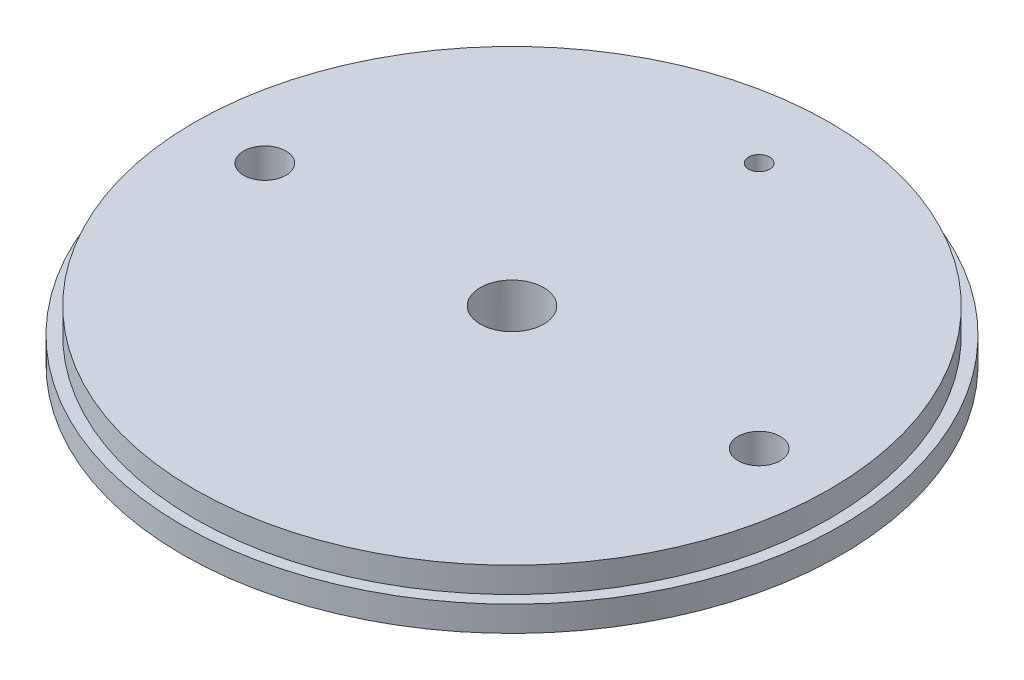
SolidWorks part; units mm, degrees
ref_plane "Front Plane" through (0, 0, 0) normal (0, 0, 1) x (1, 0, 0)
ref_plane "Top Plane" through (0, 0, 0) normal (0, 1, 0) x (1, 0, 0)
ref_plane "Right Plane" through (0, 0, 0) normal (1, 0, 0) x (0, 0, -1)
sketch "Sketch9" plane through (0, 0, 0) normal (0, 1, 0) x (1, 0, 0)
  circle A0 centre (0, 0) radius 49.53
  dimension "D1" = 99.06
extrude "Boss-Extrude1" add sketch "Sketch9" along normal blind 3.81
sketch "Sketch10" plane through (0, 3.81, 0) normal (0, 1, 0) x (1, 0, 0)
  circle A0 centre (0, 0) radius 47.752
  dimension "D1" = 95.504
extrude "Boss-Extrude2" add sketch "Sketch10" along normal blind 3.81
sketch "Sketch11" plane through (0, 0, 0) normal (0, -1, 0) x (-1, 0, 0)
  circle A0 centre (0, 0) radius 37.1475
  circle A1 centre (-37.1475, 0) radius 3.175
  circle A2 centre (37.1475, 0) radius 3.175
  circle A3 centre (0, 37.1475) radius 1.5875
  circle A4 centre (0, 0) radius 4.7625
  dimension "D1" = 74.295
  dimension "D2" = 6.35
  dimension "D3" = 6.35
  dimension "D4" = 3.175
extrude "Cut-Extrude1" cut sketch "Sketch11" against normal blind 10.922 contours A0 A2 | A0 A2 | A0 A1 | A0 A1 | A4 region at (-35.7758, 0, 0) region at (-38.4703, 0, 0) region at (38.4703, 0, 0) region at (35.7758, 0, 0) region at (0, 0, 0)
extrude "Cut-Extrude2" cut sketch "Sketch11<3>" against normal blind 40.64 contours A0 A3 | A0 A3 | A0 A2 | A0 A2 | A0 A1 | A0 A1 region at (-35.7758, 0, 0) region at (-38.4703, 0, 0) region at (0, 0, -36.4677) region at (0, 0, -37.8151) region at (38.4703, 0, 0) region at (35.7758, 0, 0)
sketch "Sketch11<3>" plane through (0, 0, 0) normal (0, -1, 0) x (-1, 0, 0) same geometry as "Sketch11"
